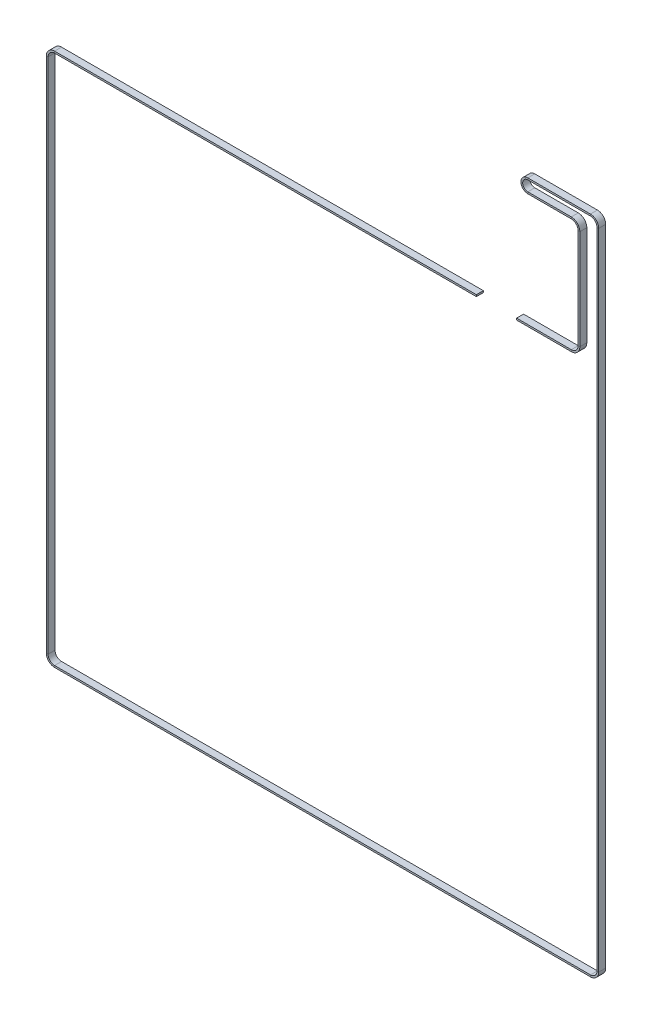
SolidWorks part; units mm, degrees
ref_plane "Front" through (0, 0, 0) normal (0, 0, 1) x (1, 0, 0)
ref_plane "Top" through (0, 0, 0) normal (0, 1, 0) x (1, 0, 0)
ref_plane "Right" through (0, 0, 0) normal (1, 0, 0) x (0, 0, -1)
sketch "Sketch1" plane through (0, 0, 2.2) normal (0, 0, 1) x (1, 0, 0)
  line L0 (377.3122, -142.2854) -> (431.3122, -142.2854)
  line L1 (377.3122, -152.6854) -> (414.8122, -152.6854)
  line L2 (421.4122, -159.2854) -> (421.4122, -245.207)
  line L3 (437.6872, -148.6604) -> (437.6872, -703.9854)
  line L4 (-37.0628, -703.9854) -> (-37.0628, -258.032)
  line L5 (431.3122, -710.3604) -> (-30.6878, -710.3604)
  line L6 (-30.6878, -251.657) -> (332.9622, -251.657)
  line L7 (367.6622, -250.207) -> (367.6622, -255.207) construction
  line L9 (414.8122, -251.807) -> (367.6622, -251.807)
  line L10 (332.9622, -255.207) -> (332.9622, -250.207) construction
  circle A0 centre (414.8122, -159.2854) radius 6.6 construction
  circle A1 centre (431.3122, -148.6604) radius 6.375 construction
  circle A2 centre (377.3122, -147.4854) radius 5.2 construction
  arc A3 (431.3122, -142.2854) -> (437.6872, -148.6604) centre (431.3122, -148.6604) cw
  arc A4 (377.3122, -152.6854) -> (377.3122, -142.2854) centre (377.3122, -147.4854) cw
  arc A5 (414.8122, -152.6854) -> (421.4122, -159.2854) centre (414.8122, -159.2854) cw
  circle A6 centre (-30.6878, -703.9854) radius 6.375 construction
  arc A7 (-30.6878, -710.3604) -> (-37.0628, -703.9854) centre (-30.6878, -703.9854) cw
  circle A8 centre (431.3122, -148.6604) radius 9 construction
  circle A9 centre (414.8122, -159.2854) radius 9 construction
  circle A10 centre (-30.6878, -258.032) radius 6.375 construction
  circle A11 centre (431.3122, -703.9854) radius 6.375 construction
  arc A12 (437.6872, -703.9854) -> (431.3122, -710.3604) centre (431.3122, -703.9854) cw
  arc A13 (-37.0628, -258.032) -> (-30.6878, -251.657) centre (-30.6878, -258.032) cw
  circle A14 centre (414.8122, -245.207) radius 6.6 construction
  arc A15 (421.4122, -245.207) -> (414.8122, -251.807) centre (414.8122, -245.207) cw
  circle A16 centre (414.8122, -245.207) radius 5.9875 construction
  circle A17 centre (-30.6878, -258.032) radius 5.9875 construction
  dimension "D1" = 12.75
ref_plane "Plane1" through (332.9622, -251.657, 2.2) normal (1, 0, 0) x (0, 0, -1)
sketch "Sketch4" plane through (332.9622, -251.657, 2.2) normal (1, 0, 0) x (0, 0, -1)
  line L0 (0, 102.9966) -> (0, -452.3284) construction
  line L1 (3, -0.75) -> (-3, -0.75)
  line L2 (3, -0.75) -> (3, 0.75)
  line L3 (3, 0.75) -> (-3, 0.75)
  line L4 (-3, -0.75) -> (-3, 0.75)
  line L5 (3, -0.75) -> (-3, 0.75) construction
  line L6 (3, 0.75) -> (-3, -0.75) construction
  line L7 (0, 0) -> (0, -12.75) construction
  point P0 (0, 0)
  dimension "D1" = 1.5
  dimension "D2" = 6
sweep "Sweep1" add profiles "Sketch4" path "Sketch1"
